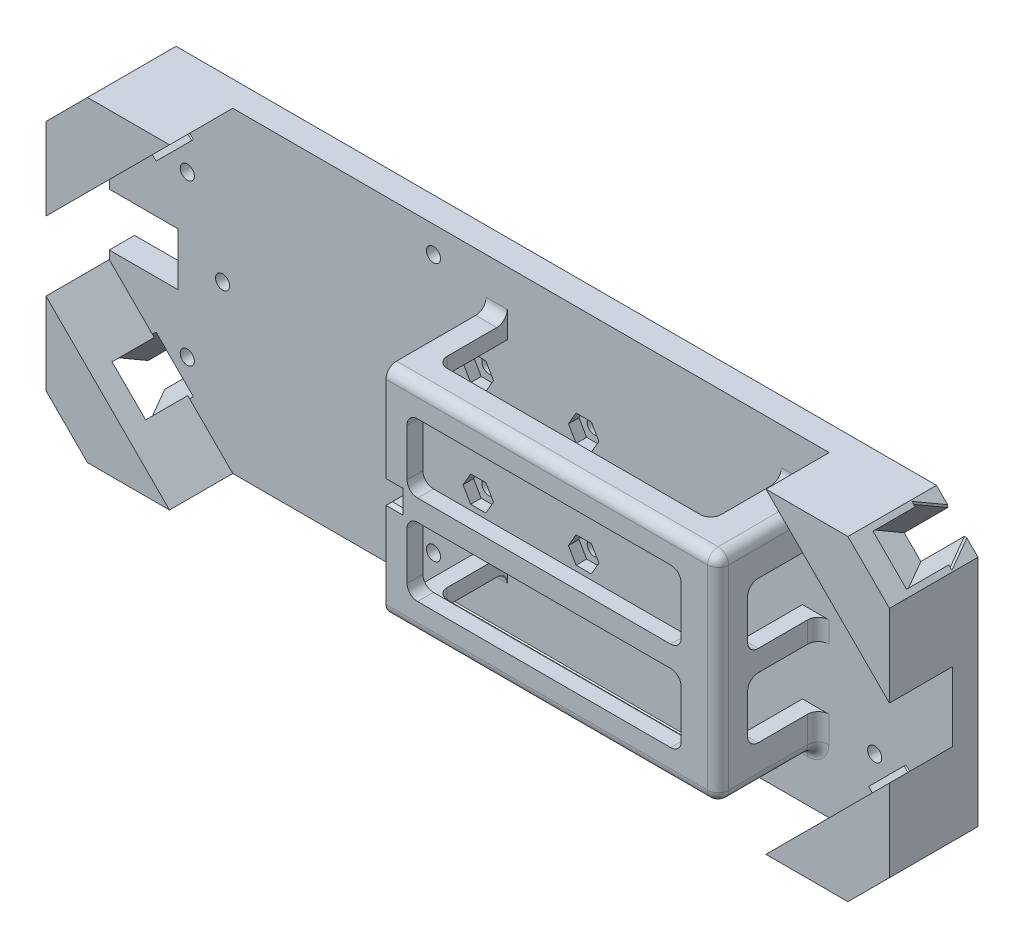
SolidWorks part; units mm, degrees
ref_plane "Front Plane" through (0, 0, 0) normal (0, 0, 1) x (1, 0, 0)
ref_plane "Top Plane" through (0, 0, 0) normal (0, 1, 0) x (1, 0, 0)
ref_plane "Right Plane" through (0, 0, 0) normal (1, 0, 0) x (0, 0, -1)
sketch "Sketch1" plane through (10.8587, 0, 0) normal (0, 0, 1) x (1, 0, 0)
  line L0 (-52.705, 21.59) -> (48.895, 21.59)
  line L1 (52.705, -25.4) -> (-52.705, -25.4)
  line L2 (52.705, -25.4) -> (52.705, 25.4)
  line L3 (52.705, 25.4) -> (-52.705, 25.4)
  line L4 (-52.705, -25.4) -> (-52.705, 25.4)
  line L5 (52.705, -25.4) -> (-52.705, 25.4) construction
  line L6 (52.705, 25.4) -> (-52.705, -25.4) construction
  line L7 (48.895, 21.59) -> (48.895, -22.86)
  line L8 (48.895, -22.86) -> (-52.705, -22.86)
  line L9 (-52.705, 13.97) -> (-6.985, 13.97)
  line L10 (-6.985, 13.97) -> (-6.985, -6.35)
  line L11 (-6.985, -6.35) -> (-52.705, -6.35)
  point P0 (0, 0)
  dimension "D1" = 105.41
  dimension "D2" = 50.8
  dimension "D3" = 101.6
  dimension "D4" = 44.45
  dimension "D5" = 3.81
  dimension "D6" = 45.72
  dimension "D7" = 20.32
  dimension "D8" = 7.62
extrude "Boss-Extrude1" add sketch "Sketch1" along normal blind 27.432 contours L7 L8 L4 L1 L2 L3 L0 region at (-40.6761, 23.495, 0)
extrude "Boss-Extrude2" add sketch "Sketch1<3>" along normal blind 5.08 contours L10 L11 L4 L8 L7 L0 L9 region at (16.19, -1.7862, 0)
sketch "Sketch1<3>" plane through (10.8587, 0, 0) normal (0, 0, 1) x (1, 0, 0) same geometry as "Sketch1"
sketch "Sketch4" plane through (10.8587, 0, 5.08) normal (0, 0, 1) x (1, 0, 0)
  line L0 (-52.705, 21.59) -> (48.895, 21.59) construction
  line L1 (-44.7859, 21.59) -> (-47.9241, 21.59)
  line L2 (-47.9241, 21.59) -> (-49.4932, 18.8722)
  line L3 (-49.4932, 18.8722) -> (-47.9241, 16.1544)
  line L4 (-47.9241, 16.1544) -> (-44.7859, 16.1544)
  line L5 (-44.7859, 16.1544) -> (-43.2168, 18.8722)
  line L6 (-43.2168, 18.8722) -> (-44.7859, 21.59)
  line L7 (-52.705, 13.97) -> (-52.705, 21.59) construction
  line L8 (-13.3987, 22.7847) -> (-13.3987, -11.3368) construction
  line L9 (21.1266, 16.1544) -> (17.9884, 16.1544)
  line L10 (17.9884, 16.1544) -> (16.4193, 18.8722)
  line L11 (16.4193, 18.8722) -> (17.9884, 21.59)
  line L12 (17.9884, 21.59) -> (21.1266, 21.59)
  line L13 (21.1266, 21.59) -> (22.6958, 18.8722)
  line L14 (22.6958, 18.8722) -> (21.1266, 16.1544)
  line L15 (0, 0) -> (10.9329, 0) construction
  line L16 (22.6958, -18.8722) -> (21.1266, -16.1544)
  line L17 (21.1266, -21.59) -> (22.6958, -18.8722)
  line L18 (17.9884, -21.59) -> (21.1266, -21.59)
  line L19 (16.4193, -18.8722) -> (17.9884, -21.59)
  line L20 (17.9884, -16.1544) -> (16.4193, -18.8722)
  line L21 (21.1266, -16.1544) -> (17.9884, -16.1544)
  line L22 (-49.4932, -18.8722) -> (-47.9241, -16.1544)
  line L23 (-47.9241, -21.59) -> (-49.4932, -18.8722)
  line L24 (-43.2168, -18.8722) -> (-44.7859, -21.59)
  line L25 (-44.7859, -16.1544) -> (-43.2168, -18.8722)
  line L26 (-47.9241, -16.1544) -> (-44.7859, -16.1544)
  line L27 (-44.7859, -21.59) -> (-47.9241, -21.59)
  circle A0 centre (-46.355, 18.8722) radius 2.7178 construction
  circle A1 centre (-46.355, 18.8722) radius 1.524
  circle A2 centre (19.5575, 18.8722) radius 1.524
  circle A3 centre (-46.355, -18.8722) radius 1.524
  circle A4 centre (19.5575, -18.8722) radius 1.524
  dimension "D4" = 3.048
  dimension "D1" = 5.4356
  dimension "D2" = 6.35
  dimension "D3" = 2.54
extrude "Cut-Extrude1" cut sketch "Sketch4" against normal blind 2.286 contours L5 L6 L14 L2 L3 L4 A1 | L14 L13 L11 L10 L9 A2 | L26 L22 L23 L12 L24 L25 A3 | L16 L21 L20 L19 L12 L17 A4 region at (-33.2145, 20.1896, 5.08) region at (30.4163, 16.2374, 5.08) region at (32.698, -20.1896, 5.08) region at (-37.778, -17.5548, 5.08)
extrude "Cut-Extrude2" cut sketch "Sketch4<4>" against normal through all contours A1 | A2 | A3 | A4 region at (-35.4963, 18.8722, 5.08) region at (30.4163, 18.8722, 5.08) region at (-35.4963, -18.8722, 5.08) region at (30.4163, -18.8722, 5.08)
sketch "Sketch4<4>" plane through (10.8587, 0, 5.08) normal (0, 0, 1) x (1, 0, 0) same geometry as "Sketch4"
sketch "Sketch7" plane through (10.8587, 0, 27.432) normal (0, 0, 1) x (1, 0, 0)
  line L0 (0, 0) -> (-46.355, 0) construction
  line L1 (-52.705, 25.4) -> (52.705, 25.4)
  line L2 (-52.705, 25.4) -> (-52.705, 6.35)
  line L3 (-52.705, -25.4) -> (52.705, -25.4)
  line L4 (52.705, 25.4) -> (52.705, -25.4)
  line L5 (-52.705, 6.35) -> (-46.355, 6.35)
  line L7 (-52.705, -6.35) -> (-46.355, -6.35)
  line L8 (-46.355, 6.35) -> (-46.355, -6.35)
  line L9 (-52.705, -6.35) -> (-52.705, -25.4)
  line L10 (-28.575, 0) -> (-1035.3573, 0) construction
  point P11 (-46.355, 0)
  dimension "D1" = 12.7
  dimension "D2" = 6.35
extrude "Boss-Extrude3" add sketch "Sketch7" along normal blind 3.81
fillet "Fillet1" radius 2.54 5 edges at (10.8587, -25.4, 31.242) (63.5637, -25.4, 15.621) (63.5637, 0, 31.242) (63.5637, 25.4, 15.621) (10.8587, 25.4, 31.242)
chamfer "Chamfer3" distance 1.27 angle 45 9 edges at (-41.8463, 21.59, 16.256) (-41.8463, -22.86, 16.256) (-41.8463, 13.97, 27.432) (-41.8463, -14.605, 27.432) (-41.8463, -6.35, 29.337) (-38.6713, -6.35, 31.242) (-35.4963, 0, 31.242) (-38.6713, 6.35, 31.242) (-41.8463, 6.35, 29.337)
chamfer "Chamfer4" distance 0.254 angle 45 4 edges at (-33.9723, -18.8722, 0) (31.9403, -18.8722, 0) (-33.9723, 18.8722, 0) (31.9403, 18.8722, 0)
sketch "Sketch8" plane through (10.8587, 0, 5.08) normal (0, 0, 1) x (1, 0, 0)
  line L0 (-52.705, -7.62) -> (-52.705, -22.86) construction
  line L1 (48.895, 21.59) -> (-52.705, 21.59)
  line L2 (48.895, 21.59) -> (48.895, -22.86)
  line L3 (48.895, -22.86) -> (-52.705, -22.86)
  line L4 (-52.705, 21.59) -> (-52.705, -22.86)
  line L5 (48.895, -22.86) -> (-51.435, -22.86) construction
extrude "Cut-Extrude3" cut sketch "Sketch8" against normal up to surface (5.08 mm away) up to face at (-33.7183, -18.8722, 0)
chamfer "Chamfer5" distance 1.27 angle 45 2 edges at (-41.8463, -22.86, 2.54) (-41.8463, 21.59, 2.54)
sketch "Sketch9" plane through (10.8587, 0, 0) normal (0, 0, -1) x (-1, 0, 0)
  line L0 (-90.7413, 28.1) -> (-80.7413, 38.1)
  line L1 (-80.7413, -38.1) -> (102.4587, -38.1)
  line L2 (-90.7413, -28.1) -> (-90.7413, 28.1)
  line L3 (-80.7413, 38.1) -> (102.4587, 38.1)
  line L4 (112.4587, -28.1) -> (112.4587, 28.1)
  line L5 (-90.7413, -38.1) -> (112.4587, 38.1) construction
  line L6 (-90.7413, 38.1) -> (112.4587, -38.1) construction
  line L7 (-90.7413, -28.1) -> (-80.7413, -38.1)
  line L8 (102.4587, 38.1) -> (112.4587, 28.1)
  line L9 (102.4587, -38.1) -> (112.4587, -28.1)
  point P0 (10.8587, 0)
  dimension "D1" = 203.2
  dimension "D2" = 76.2
extrude "Boss-Extrude4" add sketch "Sketch9" along normal blind 6.096
fillet "Fillet2" radius 1.27 5 edges at (9.5887, -25.4, 0) (62.8198, -24.6561, 0) (63.5637, 0, 0) (62.8198, 24.6561, 0) (9.5887, 25.4, 0)
sketch "Sketch11" plane through (0, 0, 0) normal (0, 0, 1) x (1, 0, 0)
  line L0 (-101.6, 28.1) -> (-91.6, 38.1)
  line L1 (-91.6, 38.1) -> (-84.9257, 38.1)
  line L4 (-101.6, -28.1) -> (-101.6, 28.1) construction
  line L5 (-101.6, 21.4257) -> (-101.6, 28.1)
  line L6 (0, 0) -> (0, 53.0626) construction
  line L7 (-1000, 0) -> (0, 0) construction
  line L25 (-76.5885, 29.7628) -> (-93.2628, 13.0885)
  line L26 (-84.9257, 38.1) -> (-76.5885, 29.7628)
  line L28 (-101.6, 21.4257) -> (-93.2628, 13.0885)
  line L54 (0, -17.1831) -> (0, 17.1831) construction
  line L55 (84.9257, 38.1) -> (76.5885, 29.7628)
  line L56 (91.6, 38.1) -> (84.9257, 38.1)
  line L57 (101.6, 28.1) -> (91.6, 38.1)
  line L58 (101.6, 21.4257) -> (101.6, 28.1)
  line L59 (101.6, 21.4257) -> (93.2628, 13.0885)
  line L60 (76.5885, 29.7628) -> (93.2628, 13.0885)
  line L61 (17.1831, 0) -> (-17.1831, 0) construction
  line L62 (91.6, -38.1) -> (84.9257, -38.1)
  line L63 (101.6, -28.1) -> (91.6, -38.1)
  line L64 (101.6, -21.4257) -> (101.6, -28.1)
  line L65 (101.6, -21.4257) -> (93.2628, -13.0885)
  line L66 (76.5885, -29.7628) -> (93.2628, -13.0885)
  line L67 (84.9257, -38.1) -> (76.5885, -29.7628)
  line L68 (-84.9257, -38.1) -> (-76.5885, -29.7628)
  line L69 (-91.6, -38.1) -> (-84.9257, -38.1)
  line L70 (-101.6, -28.1) -> (-91.6, -38.1)
  line L71 (-101.6, -21.4257) -> (-101.6, -28.1)
  line L72 (-101.6, -21.4257) -> (-93.2628, -13.0885)
  line L73 (-76.5885, -29.7628) -> (-93.2628, -13.0885)
  dimension "D1" = 16.51
  dimension "D2" = 8.3372
extrude "Boss-Extrude5" [suppressed] add sketch "Sketch11" along normal blind 19.05
sketch "Sketch13" plane through (-64.85, 64.85, 0) normal (-0.7071, 0.7071, 0) x (0, 0, 1)
  line L0 (-6.096, -44.9013) -> (-6.096, -42.0708)
  line L1 (-6.096, -51.9723) -> (-6.096, -37.8302) construction
  line L2 (-6.096, -42.0708) -> (0, -38.5513)
  line L3 (0, -38.5513) -> (0, -51.2513)
  line L4 (0, -51.2513) -> (-6.096, -47.7318)
  line L5 (-6.096, -47.7318) -> (-6.096, -44.9013)
  dimension "D1" = 6.096
  dimension "D2" = 120
  dimension "D3" = 120
  dimension "D4" = 12.7
extrude "Cut-Extrude4" cut sketch "Sketch13" against normal blind 15.24
mirror "Mirror2" about plane through (0, 0, 0) normal (0, 1, 0) of "Cut-Extrude4"
mirror "Mirror3" about plane through (0, 0, 0) normal (1, 0, 0) of "Cut-Extrude4", "Mirror2"
chamfer "Chamfer7" distance 0.381 angle 45 8 edges at (99.8458, -29.8542, -3.048) (93.3542, -36.3458, -3.048) (93.3542, 36.3458, -3.048) (99.8458, 29.8542, -3.048) (-93.3542, 36.3458, -3.048) (-99.8458, 29.8542, -3.048) (-93.3542, -36.3458, -3.048) (-99.8458, -29.8542, -3.048)
sketch "Sketch17" [suppressed] plane through (0, 0, 19.05) normal (0, 0, 1) x (1, 0, 0)
  line L0 (-96.6, 33.1) -> (-92.1099, 37.5901)
  line L1 (-91.6, 38.1) -> (-101.6, 28.1) construction
  line L3 (20.6756, 0) -> (-20.6756, 0) construction
  line L6 (-80.4355, -25.9158) -> (-89.4158, -16.9355)
  line L8 (-101.0901, 28.6099) -> (-96.6, 33.1)
  line L10 (-92.1099, -37.5901) -> (-80.4355, -25.9158)
  line L30 (-92.1099, 37.5901) -> (-80.4355, 25.9158)
  line L31 (-93.2628, 13.0885) -> (-76.5885, 29.7628) construction
  line L32 (-80.4355, 25.9158) -> (-89.4158, 16.9355)
  line L33 (-89.4158, 16.9355) -> (-101.0901, 28.6099)
  line L34 (-96.6, -33.1) -> (-92.1099, -37.5901)
  line L35 (-101.0901, -28.6099) -> (-96.6, -33.1)
  line L36 (-89.4158, -16.9355) -> (-101.0901, -28.6099)
  line L37 (0, -20.6756) -> (0, 20.6756) construction
  line L38 (92.1099, -37.5901) -> (80.4355, -25.9158)
  line L39 (96.6, -33.1) -> (92.1099, -37.5901)
  line L40 (101.0901, -28.6099) -> (96.6, -33.1)
  line L41 (89.4158, -16.9355) -> (101.0901, -28.6099)
  line L42 (80.4355, -25.9158) -> (89.4158, -16.9355)
  line L43 (80.4355, 25.9158) -> (89.4158, 16.9355)
  line L44 (92.1099, 37.5901) -> (80.4355, 25.9158)
  line L45 (96.6, 33.1) -> (92.1099, 37.5901)
  line L46 (101.0901, 28.6099) -> (96.6, 33.1)
  line L47 (89.4158, 16.9355) -> (101.0901, 28.6099)
  dimension "D1" = 12.7
extrude "Cut-Extrude7" [suppressed] cut sketch "Sketch17" against normal blind 10.922
sketch "Sketch18" [suppressed] plane through (0, 0, 8.128) normal (0, 0, 1) x (1, 0, 0)
  line L0 (-92.1099, 37.5901) -> (-101.0901, 28.6099) construction
  line L1 (-80.4355, 25.9158) -> (-92.1099, 37.5901) construction
  circle A0 centre (-89.4158, 25.9158) radius 1.778
  dimension "D1" = 3.556
  dimension "D2" = 10.16
  dimension "D3" = 6.35
extrude "Cut-Extrude8" [suppressed] cut sketch "Sketch18" against normal up to surface (8.382 mm away)
mirror "Mirror6" [suppressed] about plane through (0, 0, 0) normal (0, 1, 0)
mirror "Mirror7" [suppressed] about plane through (0, 0, 0) normal (1, 0, 0)
sketch "Sketch19" plane through (0, 0, 31.242) normal (0, 0, 1) x (1, 0, 0)
  line L1 (-67.9348, -33.6729) -> (67.9348, -33.6729)
  line L2 (-67.9348, -33.6729) -> (-67.9348, 33.6729)
  line L3 (-67.9348, 33.6729) -> (67.9348, 33.6729)
  line L4 (67.9348, -33.6729) -> (67.9348, 33.6729)
  line L5 (-67.9348, -33.6729) -> (67.9348, 33.6729) construction
  line L6 (-67.9348, 33.6729) -> (67.9348, -33.6729) construction
  point P0 (0, 0)
extrude "Cut-Extrude9" cut sketch "Sketch19" against normal up to surface (31.242 mm away) up to face at (0, 0, 0)
sketch "Sketch20" plane through (0, 0, 0) normal (0, 0, 1) x (1, 0, 0)
  line L0 (65.405, 22.86) -> (65.405, -21.59)
  line L1 (65.405, -21.59) -> (-10.795, -21.59)
  line L2 (65.405, 22.86) -> (-10.795, 22.86)
  line L3 (-10.795, 22.86) -> (-10.795, 26.67)
  line L4 (-10.795, 26.67) -> (69.215, 26.67)
  line L5 (69.215, 26.67) -> (69.215, -25.4)
  line L6 (69.215, -25.4) -> (-10.795, -25.4)
  line L7 (-10.795, -25.4) -> (-10.795, -21.59)
  line L8 (101.6, 28.1) -> (101.6, -28.1) construction
  line L9 (91.6, -38.1) -> (-91.6, -38.1) construction
  dimension "D1" = 52.07
  dimension "D2" = 44.45
  dimension "D3" = 3.81
  dimension "D4" = 80.01
  dimension "D5" = 76.2
  dimension "D6" = 32.385
  dimension "D7" = 12.7
extrude "Boss-Extrude6" add sketch "Sketch20" along normal blind 20.32
sketch "Sketch21" plane through (0, 0, 20.32) normal (0, 0, 1) x (1, 0, 0)
  line L1 (-10.795, 26.67) -> (69.215, 26.67)
  line L2 (-10.795, 26.67) -> (-10.795, -25.4)
  line L3 (-10.795, -25.4) -> (69.215, -25.4)
  line L4 (69.215, 26.67) -> (69.215, -25.4)
extrude "Boss-Extrude7" add sketch "Sketch21" along normal blind 3.81
fillet "Fillet3" radius 2.54 8 edges at (29.21, 26.67, 0) (69.215, 0.635, 0) (29.21, 26.67, 24.13) (69.215, 26.67, 12.065) (69.215, 0.635, 24.13) (69.215, -25.4, 12.065) (29.21, -25.4, 0) (29.21, -25.4, 24.13)
chamfer "Chamfer8" distance 1.27 angle 45 3 edges at (-10.795, -21.59, 10.16) (-10.795, 22.86, 10.16) (-10.795, 0.635, 20.32)
chamfer "Chamfer9" [suppressed] distance 0.254 angle 45
sketch "Sketch22" [suppressed] plane through (0, 0, -0.254) normal (0, 0, -1) x (-1, 0, 0)
  line L0 (-91.6432, -38.0568) -> (-101.5568, -28.1432) construction
  line L1 (-85.0164, -25.9158) -> (-87.2161, -22.1058)
  line L2 (-87.2161, -22.1058) -> (-91.6155, -22.1058)
  line L3 (-91.6155, -22.1058) -> (-93.8152, -25.9158)
  line L4 (-93.8152, -25.9158) -> (-91.6155, -29.7258)
  line L5 (-91.6155, -29.7258) -> (-87.2161, -29.7258)
  line L6 (-87.2161, -29.7258) -> (-85.0164, -25.9158)
  circle A0 centre (-89.4158, -25.9158) radius 3.81 construction
  circle A1 centre (-89.4158, -25.9158) radius 1.778 construction
  dimension "D1" = 7.62
  dimension "D2" = 10.16
  dimension "D3" = 0
extrude "Cut-Extrude10" [suppressed] cut sketch "Sketch22" against normal blind 3.302
mirror "Mirror8" [suppressed] about plane through (0, 0, 0) normal (0, 1, 0)
mirror "Mirror9" [suppressed] about plane through (0, 0, 0) normal (1, 0, 0)
sketch "Sketch23" plane through (0, 0, 0) normal (0, 0, 1) x (1, 0, 0)
  line L16 (90.3138, -17.8336) -> (100.8207, -28.3405)
  line L18 (-91.6, -38.1) -> (91.6, -38.1)
  line L19 (100.8207, -28.3405) -> (101.4012, -28.2988)
  line L20 (100.8207, -28.3405) -> (101.4012, -28.2988)
  line L21 (101.4012, -28.2988) -> (101.6, -28.1)
  line L22 (101.6, -28.1) -> (101.6, 28.1)
  line L23 (101.4012, -28.2988) -> (101.6, -28.1)
  line L24 (101.6, 28.1) -> (101.4012, 28.2988)
  line L25 (101.6, 28.1) -> (101.4012, 28.2988)
  line L26 (91.6, 38.1) -> (-91.6, 38.1)
  line L27 (101.4012, 28.2988) -> (100.8207, 28.3405)
  line L28 (101.4012, 28.2988) -> (100.8207, 28.3405)
  line L29 (90.3138, -17.8336) -> (100.8207, -28.3405)
  line L30 (-101.6, 28.1) -> (-101.6, -28.1)
  line L34 (-91.6, -38.1) -> (91.6, -38.1)
  line L38 (101.6, -28.1) -> (101.6, 28.1)
  line L42 (91.6, 38.1) -> (-91.6, 38.1)
  line L46 (-101.6, 28.1) -> (-101.6, -28.1)
  line L56 (91.8405, 37.3207) -> (91.7988, 37.9012)
  line L57 (91.8405, 37.3207) -> (91.7988, 37.9012)
  line L58 (91.7988, 37.9012) -> (91.6, 38.1)
  line L59 (91.7988, 37.9012) -> (91.6, 38.1)
  line L60 (-91.6, 38.1) -> (-91.7988, 37.9012)
  line L61 (-91.6, 38.1) -> (-91.7988, 37.9012)
  line L62 (-91.7988, 37.9012) -> (-91.8405, 37.3207)
  line L63 (-91.7988, 37.9012) -> (-91.8405, 37.3207)
  line L64 (100.8207, 28.3405) -> (90.3138, 17.8336)
  line L66 (-100.8207, 28.3405) -> (-101.4012, 28.2988)
  line L67 (-100.8207, 28.3405) -> (-101.4012, 28.2988)
  line L68 (-101.4012, 28.2988) -> (-101.6, 28.1)
  line L69 (-101.4012, 28.2988) -> (-101.6, 28.1)
  line L70 (-101.6, -28.1) -> (-101.4012, -28.2988)
  line L71 (-101.6, -28.1) -> (-101.4012, -28.2988)
  line L72 (-101.4012, -28.2988) -> (-100.8207, -28.3405)
  line L73 (-101.4012, -28.2988) -> (-100.8207, -28.3405)
  line L74 (100.8207, 28.3405) -> (90.3138, 17.8336)
  line L76 (-91.8405, -37.3207) -> (-91.7988, -37.9012)
  line L77 (-91.8405, -37.3207) -> (-91.7988, -37.9012)
  line L78 (-91.7988, -37.9012) -> (-91.6, -38.1)
  line L79 (-91.7988, -37.9012) -> (-91.6, -38.1)
  line L80 (91.6, -38.1) -> (91.7988, -37.9012)
  line L81 (91.6, -38.1) -> (91.7988, -37.9012)
  line L82 (91.7988, -37.9012) -> (91.8405, -37.3207)
  line L83 (91.7988, -37.9012) -> (91.8405, -37.3207)
  line L92 (90.3138, 17.8336) -> (81.3336, 26.8138)
  line L93 (90.3138, 17.8336) -> (81.3336, 26.8138)
  line L94 (81.3336, 26.8138) -> (91.8405, 37.3207)
  line L95 (81.3336, 26.8138) -> (91.8405, 37.3207)
  line L96 (-91.8405, 37.3207) -> (-81.3336, 26.8138)
  line L97 (-91.8405, 37.3207) -> (-81.3336, 26.8138)
  line L98 (-81.3336, 26.8138) -> (-90.3138, 17.8336)
  line L99 (-81.3336, 26.8138) -> (-90.3138, 17.8336)
  line L100 (-90.3138, 17.8336) -> (-100.8207, 28.3405)
  line L101 (-90.3138, 17.8336) -> (-100.8207, 28.3405)
  line L102 (-100.8207, -28.3405) -> (-90.3138, -17.8336)
  line L103 (-100.8207, -28.3405) -> (-90.3138, -17.8336)
  line L104 (-90.3138, -17.8336) -> (-81.3336, -26.8138)
  line L105 (-90.3138, -17.8336) -> (-81.3336, -26.8138)
  line L106 (-81.3336, -26.8138) -> (-91.8405, -37.3207)
  line L107 (-81.3336, -26.8138) -> (-91.8405, -37.3207)
  line L108 (91.8405, -37.3207) -> (81.3336, -26.8138)
  line L109 (91.8405, -37.3207) -> (81.3336, -26.8138)
  line L110 (81.3336, -26.8138) -> (90.3138, -17.8336)
  line L111 (81.3336, -26.8138) -> (90.3138, -17.8336)
  dimension "D1" = 0
sketch "Sketch24" plane through (0, 0, 0) normal (0, 0, 1) x (1, 0, 0)
  line L10 (-90.7628, 19.1806) -> (-101.6, 8.3434)
  line L11 (-101.6, -28.1) -> (-101.6, 28.1) construction
  line L12 (-101.6, 8.3434) -> (-101.6, 28.1)
  line L13 (-101.6, 28.1) -> (-100.6411, 29.0589)
  line L14 (-100.6411, 29.0589) -> (-90.7628, 19.1806)
  line L15 (-92.5589, 37.1411) -> (-91.6, 38.1)
  line L16 (-91.6, 38.1) -> (-71.8434, 38.1)
  line L17 (-91.6, 38.1) -> (91.6, 38.1) construction
  line L18 (-71.8434, 38.1) -> (-82.6806, 27.2628)
  line L19 (-82.6806, 27.2628) -> (-92.5589, 37.1411)
extrude "Boss-Extrude8" add sketch "Sketch24" along normal blind 10.16
sketch "Sketch26" plane through (0, 0, 10.16) normal (0, 0, 1) x (1, 0, 0)
  line L0 (-101.6, 8.3434) -> (-71.8434, 38.1)
  line L1 (-71.8434, 38.1) -> (-91.6, 38.1)
  line L2 (-91.6, 38.1) -> (-101.6, 28.1)
  line L3 (-101.6, 28.1) -> (-101.6, 8.3434)
extrude "Boss-Extrude10" add sketch "Sketch26" along normal blind 5.08
mirror "Mirror12" about plane through (0, 0, 0) normal (0, 1, 0) of "Boss-Extrude8", "Boss-Extrude10"
mirror "Mirror13" about plane through (0, 0, 0) normal (1, 0, 0) of "Mirror12"
sketch "Sketch27" plane through (0, 0, 0) normal (0, 0, 1) x (1, 0, 0)
  circle A0 centre (-23.495, 31.75) radius 1.7
  circle A1 centre (-23.495, -30.48) radius 1.7
  dimension "D1" = 3.4
extrude "Cut-Extrude11" cut sketch "Sketch27" against normal up to next
sketch "Sketch28" plane through (0, 0, -6.096) normal (0, 0, -1) x (-1, 0, 0)
  circle A0 centre (23.495, -30.48) radius 3.302
  circle A1 centre (23.495, 31.75) radius 3.302
  dimension "D1" = 6.604
extrude "Cut-Extrude12" cut sketch "Sketch28" against normal blind 3.302
sketch "Sketch29" plane through (0, 0, 24.13) normal (0, 0, 1) x (1, 0, 0)
  line L0 (-10.795, 24.13) -> (-10.795, -22.86) construction
  line L1 (-5.715, 19.685) -> (60.325, 19.685)
  line L2 (-5.715, 19.685) -> (-5.715, 3.175)
  line L3 (-5.715, -18.415) -> (60.325, -18.415)
  line L4 (60.325, 19.685) -> (60.325, 3.175)
  line L6 (66.675, -22.86) -> (66.675, 24.13) construction
  line L7 (-10.795, -22.86) -> (66.675, -22.86) construction
  line L8 (-5.715, -1.905) -> (-5.715, -18.415)
  line L9 (-5.715, 3.175) -> (60.325, 3.175)
  line L11 (-5.715, -1.905) -> (60.325, -1.905)
  line L13 (60.325, -1.905) -> (60.325, -18.415)
  dimension "D1" = 38.1
  dimension "D2" = 6.35
  dimension "D3" = 5.08
  dimension "D4" = 4.445
  dimension "D5" = 5.08
extrude "Cut-Extrude13" cut sketch "Sketch29" against normal up to next
sketch "Sketch30" plane through (0, -25.4, 0) normal (0, -1, 0) x (1, 0, 0)
  line L0 (71.8434, 0) -> (-71.8434, 0) construction
  line L1 (-5.715, 0) -> (60.325, 0)
  line L2 (-5.715, 0) -> (-5.715, 17.018)
  line L3 (-5.715, 17.018) -> (60.325, 17.018)
  line L4 (60.325, 0) -> (60.325, 17.018)
  line L5 (-10.795, 21.59) -> (-10.795, 2.54) construction
  line L6 (66.675, 2.54) -> (66.675, 21.59) construction
  line L7 (66.675, 21.59) -> (-10.795, 21.59) construction
  dimension "D1" = 5.08
  dimension "D2" = 6.35
  dimension "D3" = 4.572
extrude "Cut-Extrude14" cut sketch "Sketch30" against normal through all
sketch "Sketch31" plane through (69.215, 0, 0) normal (1, 0, 0) x (0, 0, -1)
  line L0 (-21.59, 24.13) -> (-21.59, -22.86) construction
  line L1 (-17.018, 17.78) -> (0, 17.78)
  line L2 (-17.018, 17.78) -> (-17.018, 3.175)
  line L3 (-17.018, -16.51) -> (0, -16.51)
  line L4 (0, 17.78) -> (0, 3.175)
  line L5 (0, 8.3434) -> (0, -8.3434) construction
  line L6 (-2.54, 24.13) -> (-21.59, 24.13) construction
  line L7 (-21.59, -22.86) -> (-2.54, -22.86) construction
  line L9 (-17.018, -1.905) -> (0, -1.905)
  line L11 (-17.018, 3.175) -> (0, 3.175)
  line L15 (-17.018, -1.905) -> (-17.018, -16.51)
  line L16 (0, -1.905) -> (0, -16.51)
  point P12 (-17.018, 0.635)
  dimension "D1" = 4.572
  dimension "D2" = 0
  dimension "D3" = 6.35
  dimension "D4" = 6.35
  dimension "D5" = 5.08
extrude "Cut-Extrude15" cut sketch "Sketch31" against normal up to next
sketch "Sketch32" plane through (0, -25.4, 0) normal (0, 1, 0) x (1, 0, 0)
  line L1 (-5.715, 0) -> (60.325, 0)
  line L2 (-5.715, 0) -> (-5.715, -2.54)
  line L3 (-5.715, -2.54) -> (60.325, -2.54)
  line L4 (60.325, 0) -> (60.325, -2.54)
extrude "Cut-Extrude16" cut sketch "Sketch32" against normal through all
sketch "Sketch33" plane through (69.215, 0, 0) normal (-1, 0, 0) x (0, 0, 1)
  line L0 (17.018, 17.78) -> (0, 17.78) construction
  line L1 (2.6099, 17.78) -> (0, 17.78)
  line L2 (2.6099, 17.78) -> (2.6099, -16.51)
  line L3 (2.6099, -16.51) -> (0, -16.51)
  line L4 (0, 17.78) -> (0, -16.51)
  line L5 (0, -16.51) -> (17.018, -16.51) construction
  point P6 (1.3049, -16.51)
  dimension "D1" = 0
  dimension "D2" = 0
extrude "Cut-Extrude17" cut sketch "Sketch33" against normal blind 3.302
sketch "Sketch34" plane through (0, 0, 0) normal (0, 0, 1) x (1, 0, 0)
  circle A0 centre (-74.295, 0.635) radius 1.7
extrude "Cut-Extrude18" cut sketch "Sketch34" against normal through all
sketch "Sketch35" plane through (0, 0, -6.096) normal (0, 0, -1) x (-1, 0, 0)
  circle A0 centre (74.295, 0.635) radius 3.302
  dimension "D1" = 6.604
extrude "Cut-Extrude19" cut sketch "Sketch35" against normal blind 3.302
fillet "Fillet4" radius 2.54 17 edges at (-5.715, 3.175, 22.225) (-5.715, -18.415, 22.225) (60.325, 3.175, 22.225) (60.325, -18.415, 22.225) (60.325, -1.905, 22.225) (60.325, 19.685, 22.225) (-5.715, 19.685, 22.225) (-5.715, -1.905, 22.225) (-5.715, -23.495, 17.018) (60.325, -23.495, 17.018) (-5.715, 24.765, 17.018) (60.325, 24.765, 17.018) (67.31, -16.51, 17.018) (67.31, 3.175, 17.018) (67.31, 17.78, 17.018) (67.31, -1.905, 17.018) (69.215, 0.635, 0)
hole_wizard "CBORE for M3 SHCS1" positions "Sketch36" profile "Sketch37" counterbore size "M3" standard "ANSI Metric" end condition up to next
sketch "Sketch36" plane through (0, 0, -6.096) normal (0, 0, -1) x (-1, 0, 0)
  line L0 (-91.6, -38.1) -> (91.6, -38.1) construction
  line L1 (101.6, -28.1) -> (101.6, 28.1) construction
  point P0 (82.804, -19.304)
  dimension "D1" = 18.796
  dimension "D2" = 18.796
sketch "Sketch37" plane through (-82.804, -19.304, -6.096) normal (1, 0, 0) x (0, 1, 0)
  line L0 (0, 0) -> (0, 6.097)
  line L1 (0, 6.097) -> (1.7, 6.097)
  line L3 (1.7, 6.097) -> (1.7, 3)
  line L4 (1.7, 3) -> (3.25, 3)
  line L5 (3.25, 3) -> (3.25, 0)
  line L7 (3.25, 0) -> (0, 0)
  line L11 (0, -6.35) -> (0, 107.95) construction
  dimension "Thru Hole Dia." = 3.4
  dimension "Thru Hole Depth" = 6.097
  dimension "C'Bore Dia." = 6.5
  dimension "C'Bore Depth" = 3
mirror "Mirror14" about plane through (0, 0, 0) normal (0, 1, 0) of "CBORE for M3 SHCS1"
mirror "Mirror15" about plane through (0, 0, 0) normal (1, 0, 0) of "Mirror14"
sketch "Sketch38" plane through (0, 0, -6.096) normal (0, 0, -1) x (-1, 0, 0)
  line L1 (-5.715, -3.81) -> (5.715, -3.81)
  line L2 (-5.715, -3.81) -> (-5.715, 3.81)
  line L3 (-5.715, 3.81) -> (5.715, 3.81)
  line L4 (5.715, -3.81) -> (5.715, 3.81)
  line L5 (-5.715, -3.81) -> (5.715, 3.81) construction
  line L6 (-5.715, 3.81) -> (5.715, -3.81) construction
  point P0 (0, 0)
  dimension "D1" = 11.43
  dimension "D2" = 7.62
extrude "Cut-Extrude20" cut sketch "Sketch38" against normal up to next
chamfer "Chamfer10" distance 0.762 angle 45 4 edges at (0, -3.81, -6.096) (5.715, 0, -6.096) (0, 3.81, -6.096) (-5.715, 0, -6.096)
hole_wizard "M3 Clearance Hole1" positions "Sketch39" profile "Sketch40" hole size "M3" standard "ANSI Metric" end condition up to next
sketch "Sketch39" plane through (0, 0, -6.096) normal (0, 0, -1) x (-1, 0, 0)
  line L0 (16.6243, 0) -> (-16.6243, 0) construction
  line L2 (0, 16.6243) -> (0, -16.6243) construction
  point P0 (12.7, 12.7)
  dimension "D1" = 12.7
  dimension "D2" = 12.7
sketch "Sketch40" plane through (-12.7, 12.7, -6.096) normal (1, 0, 0) x (0, 1, 0)
  line L0 (0, 0) -> (0, 6.097)
  line L1 (0, 6.097) -> (1.7, 6.097)
  line L2 (1.7, 6.097) -> (1.7, 0)
  line L5 (1.7, 0) -> (0, 0)
  line L11 (0, -6.35) -> (0, 107.95) construction
  dimension "Thru Hole Dia." = 3.4
  dimension "Thru Hole Depth" = 6.097
mirror "Mirror16" about plane through (0, 0, 0) normal (0, 1, 0) of "M3 Clearance Hole1"
mirror "Mirror17" about plane through (0, 0, 0) normal (1, 0, 0) of "Mirror16"
sketch "Sketch42" plane through (0, 0, 0) normal (0, 0, 1) x (1, 0, 0)
  line L1 (16.3662, 12.7) -> (14.5331, 15.875)
  line L2 (14.5331, 15.875) -> (10.8669, 15.875)
  line L3 (10.8669, 15.875) -> (9.0338, 12.7)
  line L4 (9.0338, 12.7) -> (10.8669, 9.525)
  line L5 (10.8669, 9.525) -> (14.5331, 9.525)
  line L6 (14.5331, 9.525) -> (16.3662, 12.7)
  circle A0 centre (12.7, 12.7) radius 3.175 construction
  dimension "D1" = 6.35
extrude "Cut-Extrude21" cut sketch "Sketch42" against normal blind 2.54
mirror "Mirror18" about plane through (0, 0, 0) normal (1, 0, 0) of "Cut-Extrude21"
mirror "Mirror19" about plane through (0, 0, 0) normal (0, 1, 0) of "Mirror18"
sketch "Sketch43" plane through (0, 0, 24.13) normal (0, 0, 1) x (1, 0, 0)
  line L0 (-10.795, 24.13) -> (-10.795, -22.86) construction
  line L1 (-14.097, -1.397) -> (-7.493, -1.397)
  line L2 (-14.097, -1.397) -> (-14.097, 2.667)
  line L3 (-14.097, 2.667) -> (-7.493, 2.667)
  line L4 (-7.493, -1.397) -> (-7.493, 2.667)
  line L5 (-14.097, -1.397) -> (-7.493, 2.667) construction
  line L6 (-14.097, 2.667) -> (-7.493, -1.397) construction
  point P0 (-10.795, 0.635)
  dimension "D1" = 6.604
  dimension "D2" = 4.064
extrude "Cut-Extrude22" cut sketch "Sketch43" against normal up to next
chamfer "Chamfer11" distance 0.762 angle 45 5 edges at (-10.795, -1.397, 22.86) (-9.144, -1.397, 24.13) (-7.493, 0.635, 24.13) (-9.144, 2.667, 24.13) (-10.795, 2.667, 22.86)
sketch "Sketch44" plane through (0, 0, 0) normal (0, 0, 1) x (1, 0, 0)
  line L0 (-101.6, -8.3434) -> (-101.6, 8.3434) construction
  line L1 (-118.142, -6.35) -> (-85.058, -6.35)
  line L2 (-118.142, -6.35) -> (-118.142, 6.35)
  line L3 (-118.142, 6.35) -> (-85.058, 6.35)
  line L4 (-85.058, -6.35) -> (-85.058, 6.35)
  line L5 (-118.142, -6.35) -> (-85.058, 6.35) construction
  line L6 (-118.142, 6.35) -> (-85.058, -6.35) construction
  point P0 (-101.6, 0)
  dimension "D1" = 12.7
extrude "Cut-Extrude23" cut sketch "Sketch44" against normal through all
